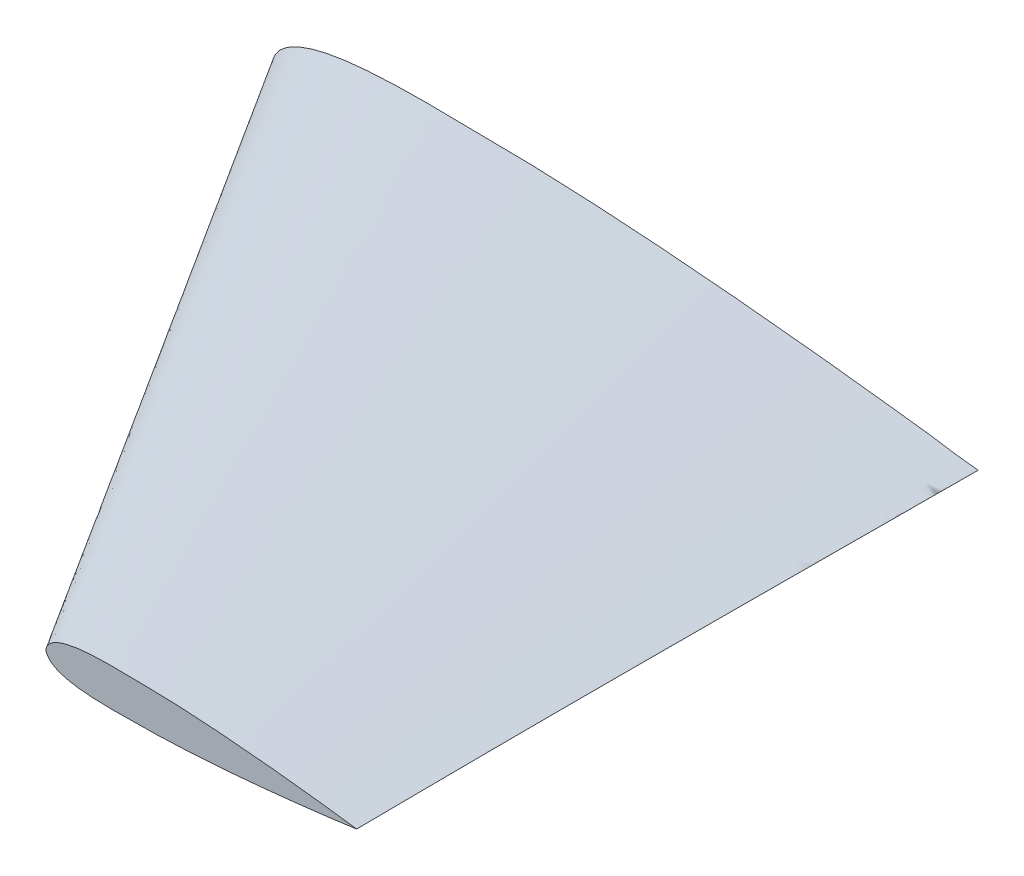
SolidWorks part; units mm, degrees
ref_plane "Front Plane" through (0, 0, 0) normal (0, 0, 1) x (1, 0, 0)
ref_plane "Top Plane" through (0, 0, 0) normal (0, 1, 0) x (1, 0, 0)
ref_plane "Right Plane" through (0, 0, 0) normal (1, 0, 0) x (0, 0, -1)
curve "Curve2"
  spline degree 3 poles (111.8113, -0.3587, 0) (115.8899, 0, 0) (111.8113, 0.3587, 0) (108.9694, 0.9319, 0) (102.7704, 1.6608, 0) (97.1846, 2.3533, 0) (91.4347, 3.004, 0) (85.7289, 3.6179, 0) (80.0114, 4.1943, 0) (74.2971, 4.7315, 0) (68.5818, 5.2229, 0) (62.867, 5.6692, 0) (57.1138, 6.0628, 0) (51.3608, 6.3997, 0) (45.6073, 6.6491, 0) (39.8919, 6.8333, 0) (35.1659, 6.8301, 0) (31.3946, 6.9179, 0) (28.5751, 6.9572, 0) (25.7175, 6.9778, 0) (22.8597, 6.9652, 0) (20.0015, 6.9059, 0) (17.1425, 6.7852, 0) (14.2823, 6.579, 0) (11.6114, 6.2817, 0) (9.13, 5.8748, 0) (7.2234, 5.4409, 0) (5.7039, 4.9815, 0) (4.5539, 4.5612, 0) (3.397, 4.0341, 0) (2.2197, 3.3435, 0) (1.2431, 2.5358, 0) (0.383, 1.4547, 0) (-0.2501, 0, 0) (0.383, -1.4547, 0) (1.2431, -2.5358, 0) (2.2197, -3.3435, 0) (3.397, -4.0341, 0) (4.5539, -4.5612, 0) (5.7039, -4.9815, 0) (7.2234, -5.4409, 0) (9.13, -5.8748, 0) (11.6114, -6.2817, 0) (14.2823, -6.579, 0) (17.1425, -6.7852, 0) (20.0015, -6.9059, 0) (22.8597, -6.9652, 0) (25.7175, -6.9778, 0) (28.5751, -6.9572, 0) (31.3946, -6.9179, 0) (35.1659, -6.8301, 0) (39.8919, -6.8333, 0) (45.6073, -6.6491, 0) (51.3608, -6.3997, 0) (57.1138, -6.0628, 0) (62.867, -5.6692, 0) (68.5818, -5.2229, 0) (74.2971, -4.7315, 0) (80.0114, -4.1943, 0) (85.7289, -3.6179, 0) (91.4347, -3.004, 0) (97.1846, -2.3533, 0) (102.7704, -1.6608, 0) (108.9694, -0.9319, 0) (111.8113, -0.3587, 0) (115.8899, 0, 0) (111.8113, 0.3587, 0) knots -0.053265 -0.028876 -0.004461 0 0.004461 0.028876 0.053265 0.077632 0.10198 0.12631 0.150624 0.174921 0.199202 0.223466 0.247713 0.272429 0.296644 0.320845 0.345037 0.356651 0.368748 0.380844 0.392939 0.405038 0.417145 0.429273 0.441447 0.451257 0.461193 0.466249 0.471407 0.476732 0.482367 0.48872 0.492634 0.5 0.507366 0.51128 0.517633 0.523268 0.528593 0.533751 0.538807 0.548743 0.558553 0.570727 0.582855 0.594962 0.607061 0.619156 0.631252 0.643349 0.654963 0.679155 0.703356 0.727571 0.752287 0.776534 0.800798 0.825079 0.849376 0.87369 0.89802 0.922368 0.946735 0.971124 0.995539 1 1.004461 1.028876 1.053265 periodic
sketch "Sketch2" plane through (0, 0, 0) normal (0, 0, 1) x (1, 0, 0)
  line L0 (0, 0) -> (115.3441, 0) construction
  spline S0 degree 3 poles (111.8113, -0.3587) (115.8899, 0) (111.8113, 0.3587) (108.9694, 0.9319) (102.7704, 1.6608) (97.1846, 2.3533) (91.4347, 3.004) (85.7289, 3.6179) (80.0114, 4.1943) (74.2971, 4.7315) (68.5818, 5.2229) (62.867, 5.6692) (57.1138, 6.0628) (51.3608, 6.3997) (45.6073, 6.6491) (39.8919, 6.8333) (35.1659, 6.8301) (31.3946, 6.9179) (28.5751, 6.9572) (25.7175, 6.9778) (22.8597, 6.9652) (20.0015, 6.9059) (17.1425, 6.7852) (14.2823, 6.579) (11.6114, 6.2817) (9.13, 5.8748) (7.2234, 5.4409) (5.7039, 4.9815) (4.5539, 4.5612) (3.397, 4.0341) (2.2197, 3.3435) (1.2431, 2.5358) (0.383, 1.4547) (-0.2501, 0) (0.383, -1.4547) (1.2431, -2.5358) (2.2197, -3.3435) (3.397, -4.0341) (4.5539, -4.5612) (5.7039, -4.9815) (7.2234, -5.4409) (9.13, -5.8748) (11.6114, -6.2817) (14.2823, -6.579) (17.1425, -6.7852) (20.0015, -6.9059) (22.8597, -6.9652) (25.7175, -6.9778) (28.5751, -6.9572) (31.3946, -6.9179) (35.1659, -6.8301) (39.8919, -6.8333) (45.6073, -6.6491) (51.3608, -6.3997) (57.1138, -6.0628) (62.867, -5.6692) (68.5818, -5.2229) (74.2971, -4.7315) (80.0114, -4.1943) (85.7289, -3.6179) (91.4347, -3.004) (97.1846, -2.3533) (102.7704, -1.6608) (108.9694, -0.9319) (111.8113, -0.3587) (115.8899, 0) (111.8113, 0.3587) knots -0.053265 -0.028876 -0.004461 0 0.004461 0.028876 0.053265 0.077632 0.10198 0.12631 0.150624 0.174921 0.199202 0.223466 0.247713 0.272429 0.296644 0.320845 0.345037 0.356651 0.368748 0.380844 0.392939 0.405038 0.417145 0.429273 0.441447 0.451257 0.461193 0.466249 0.471407 0.476732 0.482367 0.48872 0.492634 0.5 0.507366 0.51128 0.517633 0.523268 0.528593 0.533751 0.538807 0.548743 0.558553 0.570727 0.582855 0.594962 0.607061 0.619156 0.631252 0.643349 0.654963 0.679155 0.703356 0.727571 0.752287 0.776534 0.800798 0.825079 0.849376 0.87369 0.89802 0.922368 0.946735 0.971124 0.995539 1 1.004461 1.028876 1.053265 only from (115.3441, 0) to (115.3441, 0) construction
  spline S1 degree 3 poles (111.8113, -0.3587) (115.8899, 0) (111.8113, 0.3587) (108.9694, 0.9319) (102.7704, 1.6608) (97.1846, 2.3533) (91.4347, 3.004) (85.7289, 3.6179) (80.0114, 4.1943) (74.2971, 4.7315) (68.5818, 5.2229) (62.867, 5.6692) (57.1138, 6.0628) (51.3608, 6.3997) (45.6073, 6.6491) (39.8919, 6.8333) (35.1659, 6.8301) (31.3946, 6.9179) (28.5751, 6.9572) (25.7175, 6.9778) (22.8597, 6.9652) (20.0015, 6.9059) (17.1425, 6.7852) (14.2823, 6.579) (11.6114, 6.2817) (9.13, 5.8748) (7.2234, 5.4409) (5.7039, 4.9815) (4.5539, 4.5612) (3.397, 4.0341) (2.2197, 3.3435) (1.2431, 2.5358) (0.383, 1.4547) (-0.2501, 0) (0.383, -1.4547) (1.2431, -2.5358) (2.2197, -3.3435) (3.397, -4.0341) (4.5539, -4.5612) (5.7039, -4.9815) (7.2234, -5.4409) (9.13, -5.8748) (11.6114, -6.2817) (14.2823, -6.579) (17.1425, -6.7852) (20.0015, -6.9059) (22.8597, -6.9652) (25.7175, -6.9778) (28.5751, -6.9572) (31.3946, -6.9179) (35.1659, -6.8301) (39.8919, -6.8333) (45.6073, -6.6491) (51.3608, -6.3997) (57.1138, -6.0628) (62.867, -5.6692) (68.5818, -5.2229) (74.2971, -4.7315) (80.0114, -4.1943) (85.7289, -3.6179) (91.4347, -3.004) (97.1846, -2.3533) (102.7704, -1.6608) (108.9694, -0.9319) (111.8113, -0.3587) (115.8899, 0) (111.8113, 0.3587) knots -0.053265 -0.028876 -0.004461 0 0.004461 0.028876 0.053265 0.077632 0.10198 0.12631 0.150624 0.174921 0.199202 0.223466 0.247713 0.272429 0.296644 0.320845 0.345037 0.356651 0.368748 0.380844 0.392939 0.405038 0.417145 0.429273 0.441447 0.451257 0.461193 0.466249 0.471407 0.476732 0.482367 0.48872 0.492634 0.5 0.507366 0.51128 0.517633 0.523268 0.528593 0.533751 0.538807 0.548743 0.558553 0.570727 0.582855 0.594962 0.607061 0.619156 0.631252 0.643349 0.654963 0.679155 0.703356 0.727571 0.752287 0.776534 0.800798 0.825079 0.849376 0.87369 0.89802 0.922368 0.946735 0.971124 0.995539 1 1.004461 1.028876 1.053265 only from (115.3441, 0) to (115.3441, 0)
  dimension "D1" = 115.3441
ref_plane "Plane1" through (0, 0, 101.6) normal (0, 0, 1) x (1, 0, 0)
sketch "Sketch3" plane through (0, 0, 101.6) normal (0, 0, 1) x (1, 0, 0)
  line L0 (-54.6333, 0) -> (166.1417, 0) construction
  line L1 (64.5441, 0) -> (115.3441, 0) construction
  spline S0 degree 3 poles (113.7882, -0.158) (115.5845, 0) (113.7882, 0.158) (112.5366, 0.4104) (109.8064, 0.7315) (107.3463, 1.0364) (104.8139, 1.323) (102.3009, 1.5934) (99.7828, 1.8473) (97.2661, 2.0838) (94.749, 2.3003) (92.232, 2.4968) (89.6982, 2.6702) (87.1645, 2.8185) (84.6305, 2.9284) (82.1133, 3.0095) (80.0319, 3.0081) (78.3709, 3.0468) (77.1292, 3.0641) (75.8706, 3.0732) (74.612, 3.0676) (73.3532, 3.0415) (72.094, 2.9884) (70.8343, 2.8975) (69.658, 2.7666) (68.5651, 2.5874) (67.7254, 2.3963) (67.0562, 2.194) (66.5497, 2.0089) (66.0402, 1.7767) (65.5217, 1.4725) (65.0916, 1.1168) (64.7128, 0.6407) (64.4339, 0) (64.7128, -0.6407) (65.0916, -1.1168) (65.5217, -1.4725) (66.0402, -1.7767) (66.5497, -2.0089) (67.0562, -2.194) (67.7254, -2.3963) (68.5651, -2.5874) (69.658, -2.7666) (70.8343, -2.8975) (72.094, -2.9884) (73.3532, -3.0415) (74.612, -3.0676) (75.8706, -3.0732) (77.1292, -3.0641) (78.3709, -3.0468) (80.0319, -3.0081) (82.1133, -3.0095) (84.6305, -2.9284) (87.1645, -2.8185) (89.6982, -2.6702) (92.232, -2.4968) (94.749, -2.3003) (97.2661, -2.0838) (99.7828, -1.8473) (102.3009, -1.5934) (104.8139, -1.323) (107.3463, -1.0364) (109.8064, -0.7315) (112.5366, -0.4104) (113.7882, -0.158) (115.5845, 0) (113.7882, 0.158) knots -0.053265 -0.028876 -0.004461 0 0.004461 0.028876 0.053265 0.077632 0.10198 0.12631 0.150624 0.174921 0.199202 0.223466 0.247713 0.272429 0.296644 0.320845 0.345037 0.356651 0.368748 0.380844 0.392939 0.405038 0.417145 0.429273 0.441447 0.451257 0.461193 0.466249 0.471407 0.476732 0.482367 0.48872 0.492634 0.5 0.507366 0.51128 0.517633 0.523268 0.528593 0.533751 0.538807 0.548743 0.558553 0.570727 0.582855 0.594962 0.607061 0.619156 0.631252 0.643349 0.654963 0.679155 0.703356 0.727571 0.752287 0.776534 0.800798 0.825079 0.849376 0.87369 0.89802 0.922368 0.946735 0.971124 0.995539 1 1.004461 1.028876 1.053265 only from (115.3441, 0) to (115.3441, 0)
  point P5 (0, 0)
  point P6 (64.5441, 0)
  point P7 (115.3441, 0)
  point P8 (0, 0)
  dimension "D1" = 50.8
loft "Loft1" add profiles "Sketch3", "Sketch2" connector at (114.8933, 0.0626, 101.6) connector at (115.3441, 0, 0)
